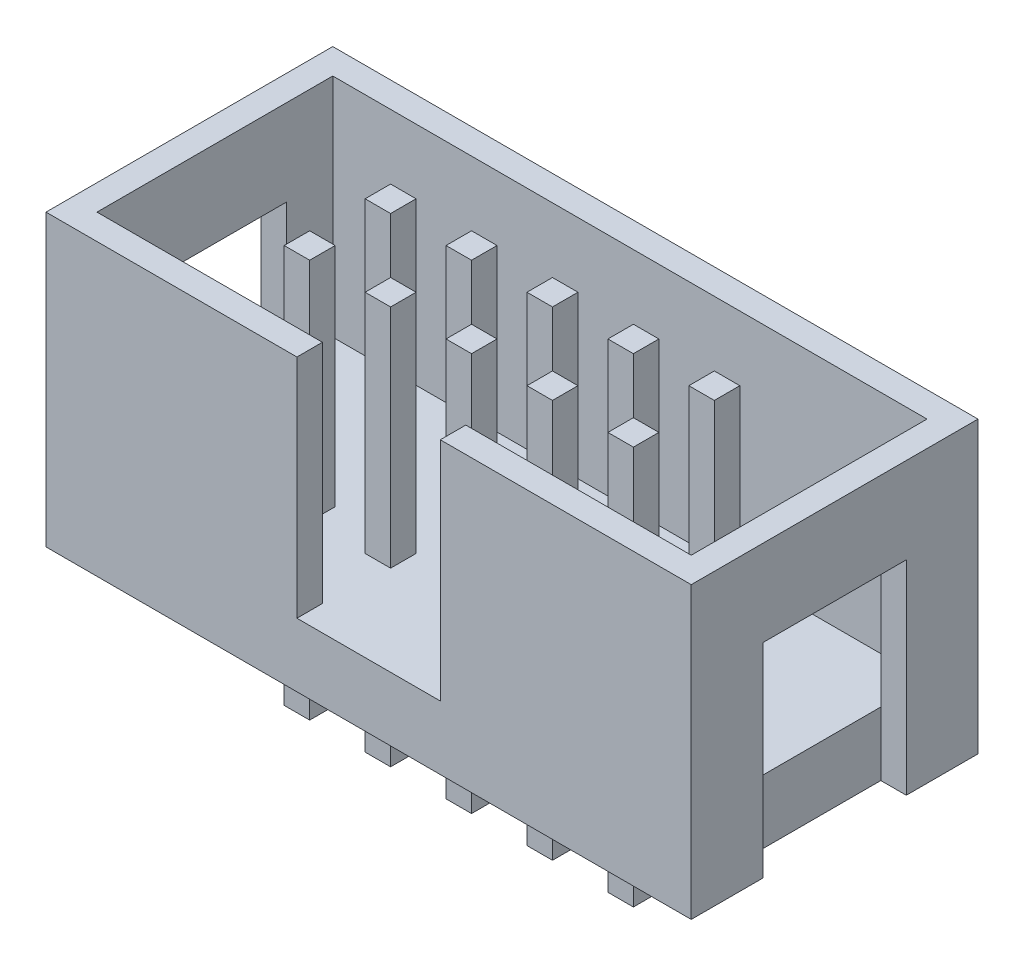
SolidWorks part; units mm, degrees
ref_plane "Front Plane" through (0, 0, 0) normal (0, 0, 1) x (1, 0, 0)
ref_plane "Top Plane" through (0, 0, 0) normal (0, 1, 0) x (1, 0, 0)
ref_plane "Right Plane" through (0, 0, 0) normal (1, 0, 0) x (0, 0, -1)
sketch "Sketch1" plane through (0, 0, 0) normal (0, 1, 0) x (1, 0, 0)
  line L1 (-39.7406, 29.0901) -> (-19.4906, 29.0901)
  line L2 (-39.7406, 29.0901) -> (-39.7406, 20.0901)
  line L3 (-39.7406, 20.0901) -> (-19.4906, 20.0901)
  line L4 (-19.4906, 29.0901) -> (-19.4906, 20.0901)
  dimension "D1" = 9
  dimension "D2" = 20.25
extrude "Boss-Extrude1" add sketch "Sketch1" along normal blind 9.1
sketch "Sketch2" plane through (0, 9.1, 0) normal (0, 1, 0) x (1, 0, 0)
  line L0 (-19.4906, 20.0901) -> (-19.4906, 29.0901) construction
  line L1 (-38.9406, 28.2901) -> (-20.2906, 28.2901)
  line L2 (-38.9406, 28.2901) -> (-38.9406, 20.8901)
  line L3 (-38.9406, 20.8901) -> (-20.2906, 20.8901)
  line L4 (-20.2906, 28.2901) -> (-20.2906, 20.8901)
  line L5 (-39.7406, 20.0901) -> (-19.4906, 20.0901) construction
  line L6 (-39.7406, 29.0901) -> (-39.7406, 20.0901) construction
  line L7 (-19.4906, 29.0901) -> (-39.7406, 29.0901) construction
  line L8 (-39.7406, 25.8601) -> (-19.4906, 25.8601) construction
  line L9 (-39.7406, 23.3201) -> (-19.4906, 23.3201) construction
  line L10 (-39.7406, 24.5901) -> (-19.4906, 24.5901) construction
  line L11 (-31.7556, 23.7201) -> (-31.7556, 22.9201)
  line L12 (-29.6156, 28.2901) -> (-29.6156, 20.8901) construction
  line L13 (-30.0156, 23.7201) -> (-30.0156, 22.9201)
  line L14 (-30.0156, 22.9201) -> (-29.2156, 22.9201)
  line L15 (-29.2156, 23.7201) -> (-29.2156, 22.9201)
  line L16 (-30.0156, 23.7201) -> (-29.2156, 23.7201)
  line L17 (-27.4756, 23.7201) -> (-27.4756, 22.9201)
  line L18 (-27.4756, 22.9201) -> (-26.6756, 22.9201)
  line L19 (-26.6756, 23.7201) -> (-26.6756, 22.9201)
  line L20 (-27.4756, 23.7201) -> (-26.6756, 23.7201)
  line L21 (-24.9356, 23.7201) -> (-24.1356, 23.7201)
  line L22 (-24.9356, 23.7201) -> (-24.9356, 22.9201)
  line L23 (-24.9356, 22.9201) -> (-24.1356, 22.9201)
  line L24 (-24.1356, 23.7201) -> (-24.1356, 22.9201)
  line L25 (-31.7556, 23.7201) -> (-32.5556, 23.7201)
  line L26 (-30.0156, 25.4601) -> (-29.2156, 25.4601)
  line L27 (-30.0156, 25.4601) -> (-30.0156, 26.2601)
  line L28 (-30.0156, 26.2601) -> (-29.2156, 26.2601)
  line L29 (-29.2156, 25.4601) -> (-29.2156, 26.2601)
  line L30 (-30.0156, 25.4601) -> (-29.2156, 26.2601) construction
  line L31 (-30.0156, 26.2601) -> (-29.2156, 25.4601) construction
  line L32 (-27.4756, 25.4601) -> (-26.6756, 25.4601)
  line L33 (-27.4756, 25.4601) -> (-27.4756, 26.2601)
  line L34 (-27.4756, 26.2601) -> (-26.6756, 26.2601)
  line L35 (-26.6756, 25.4601) -> (-26.6756, 26.2601)
  line L36 (-27.4756, 25.4601) -> (-26.6756, 26.2601) construction
  line L37 (-27.4756, 26.2601) -> (-26.6756, 25.4601) construction
  line L38 (-24.9356, 25.4601) -> (-24.1356, 25.4601)
  line L39 (-24.9356, 25.4601) -> (-24.9356, 26.2601)
  line L40 (-24.9356, 26.2601) -> (-24.1356, 26.2601)
  line L41 (-24.1356, 25.4601) -> (-24.1356, 26.2601)
  line L42 (-24.9356, 25.4601) -> (-24.1356, 26.2601) construction
  line L43 (-24.9356, 26.2601) -> (-24.1356, 25.4601) construction
  line L44 (-32.5556, 23.7201) -> (-32.5556, 22.9201)
  line L45 (-31.7556, 22.9201) -> (-32.5556, 22.9201)
  line L46 (-31.7556, 25.4601) -> (-31.7556, 26.2601)
  line L47 (-31.7556, 26.2601) -> (-32.5556, 26.2601)
  line L48 (-32.5556, 25.4601) -> (-32.5556, 26.2601)
  line L49 (-31.7556, 25.4601) -> (-32.5556, 25.4601)
  line L50 (-34.2956, 23.7201) -> (-34.2956, 22.9201)
  line L51 (-34.2956, 23.7201) -> (-35.0956, 23.7201)
  line L52 (-35.0956, 23.7201) -> (-35.0956, 22.9201)
  line L53 (-34.2956, 22.9201) -> (-35.0956, 22.9201)
  line L54 (-34.2956, 25.4601) -> (-34.2956, 26.2601)
  line L55 (-34.2956, 26.2601) -> (-35.0956, 26.2601)
  line L56 (-35.0956, 25.4601) -> (-35.0956, 26.2601)
  line L57 (-34.2956, 25.4601) -> (-35.0956, 25.4601)
  point P18 (-24.5356, 25.8601)
  point P19 (-29.6156, 25.8601)
  point P22 (-27.0756, 25.8601)
  dimension "D7" = 0.8
  dimension "D1" = 0.8
  dimension "D2" = 0.8
  dimension "D3" = 0.8
  dimension "D4" = 0.8
  dimension "D5" = 2.54
  dimension "D6" = 1.27
  dimension "D9" = 2.54
  dimension "D8" = 2.54
extrude "Cut-Extrude1" cut sketch "Sketch2" against normal blind 7.1 contours L3 L4 L1 L2
extrude "Boss-Extrude2" add sketch "Sketch2<3>" against normal blind 12.5 contours L38 L41 L40 L39 | L24 L21 L22 L23 | L20 L17 L18 L19 | L32 L35 L34 L33 | L26 L29 L28 L27 | L16 L13 L14 L15 | L45 L11 L25 L44 | L49 L46 L47 L48 | L57 L54 L55 L56 | L53 L50 L51 L52
sketch "Sketch2<3>" plane through (0, 9.1, 0) normal (0, 1, 0) x (1, 0, 0) same geometry as "Sketch2"
sketch "Sketch3" plane through (0, 0, -20.0901) normal (0, 0, 1) x (1, 0, 0)
  line L0 (-39.7406, 9.1) -> (-19.4906, 9.1) construction
  line L1 (-31.8656, 9.1) -> (-27.3656, 9.1)
  line L2 (-31.8656, 9.1) -> (-31.8656, 2)
  line L3 (-31.8656, 2) -> (-27.3656, 2)
  line L4 (-27.3656, 9.1) -> (-27.3656, 2)
  line L5 (-29.6156, 0) -> (-29.6156, 9.1) construction
  line L6 (-39.7406, 0) -> (-19.4906, 0) construction
  point P10 (-29.6156, 2)
  dimension "D1" = 7.1
  dimension "D2" = 4.5
extrude "Cut-Extrude2" cut sketch "Sketch3" against normal blind 2.1
sketch "Sketch5" plane through (-39.7406, 0, 0) normal (-1, 0, 0) x (0, 0, 1)
  line L0 (-24.5901, 0) -> (-24.5901, 9.1) construction
  line L1 (-26.8401, 0) -> (-22.3401, 0)
  line L2 (-26.8401, 0) -> (-26.8401, 6.4)
  line L3 (-26.8401, 6.4) -> (-22.3401, 6.4)
  line L4 (-22.3401, 0) -> (-22.3401, 6.4)
  line L7 (-29.0901, 0) -> (-20.0901, 0) construction
  line L8 (-29.0901, 9.1) -> (-20.0901, 9.1) construction
  point P7 (-24.5901, 6.4)
  dimension "D1" = 6.4
  dimension "D2" = 4.5
extrude "Cut-Extrude3" cut sketch "Sketch5" against normal up to surface (0.8 mm away) up to face at (-38.9406, 5.55, -24.5901)
sketch "Sketch6" plane through (-19.4906, 0, 0) normal (1, 0, 0) x (0, 0, -1)
  line L0 (24.5901, 0) -> (24.5901, 9.1) construction
  line L1 (22.3401, 0) -> (26.8401, 0)
  line L2 (22.3401, 0) -> (22.3401, 6.4)
  line L3 (22.3401, 6.4) -> (26.8401, 6.4)
  line L4 (26.8401, 0) -> (26.8401, 6.4)
  line L5 (20.0901, 0) -> (29.0901, 0) construction
  line L6 (20.0901, 9.1) -> (29.0901, 9.1) construction
  point P14 (24.5901, 6.4)
  dimension "D1" = 4.5
  dimension "D2" = 6.4
extrude "Cut-Extrude4" cut sketch "Sketch6" against normal up to surface (0.8 mm away) up to face at (-20.2906, 5.55, -24.5901)
